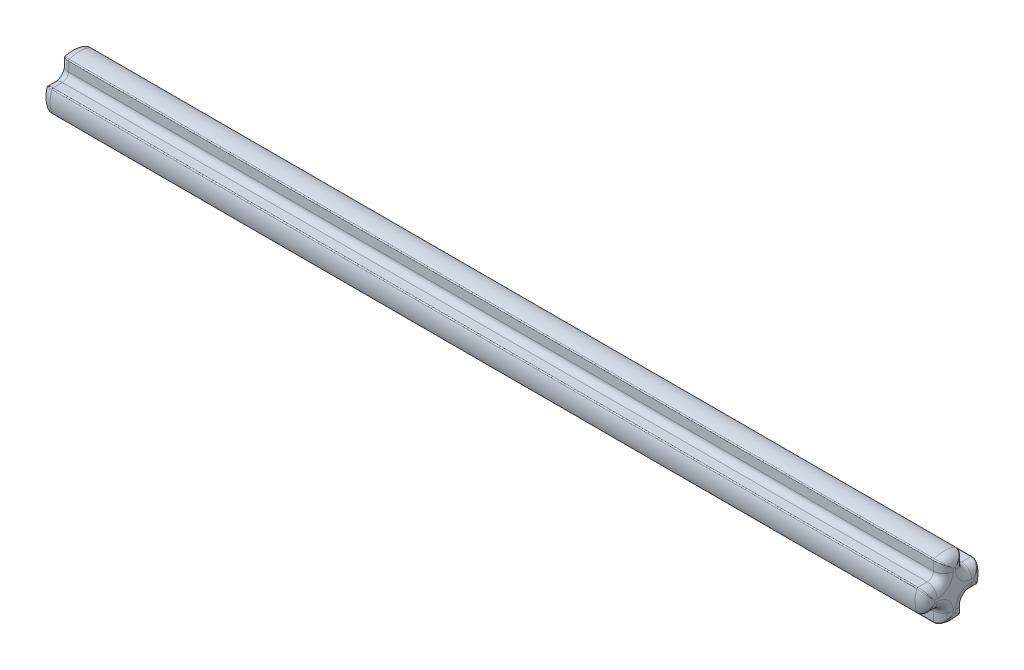
SolidWorks part; units mm, degrees
material "PET"
ref_plane "Alzado" through (0, 0, 0) normal (0, 0, 1) x (1, 0, 0)
ref_plane "Planta" through (0, 0, 0) normal (0, 1, 0) x (1, 0, 0)
ref_plane "Vista lateral" through (0, 0, 0) normal (1, 0, 0) x (0, 0, -1)
sketch "Croquis1" plane through (0, 0, 0) normal (1, 0, 0) x (0, 0, -1)
  line B0 (-1.4, 0.9) -> (-2.2249, 0.9)
  line B1 (0.9, -2.2249) -> (0.9, -1.4)
  line B2 (-0.9, -2.2249) -> (-0.9, -1.4)
  line B3 (2.2249, 0.9) -> (1.4, 0.9)
  line B4 (2.2249, -0.9) -> (1.4, -0.9)
  line B5 (-0.9, 1.4) -> (-0.9, 2.2249)
  line B6 (0.9, 1.4) -> (0.9, 2.2249)
  line B7 (-1.4, -0.9) -> (-2.2249, -0.9)
  arc B8 (-2.2249, 0.9) -> (-2.2249, -0.9) centre (0, 0) ccw
  arc B9 (-1.4, -0.9) -> (-0.9, -1.4) centre (-1.4, -1.4) cw
  arc B10 (0.9, -1.4) -> (1.4, -0.9) centre (1.4, -1.4) cw
  arc B11 (1.4, 0.9) -> (0.9, 1.4) centre (1.4, 1.4) cw
  arc B12 (-0.9, 1.4) -> (-1.4, 0.9) centre (-1.4, 1.4) cw
  arc B13 (0.9, 2.2249) -> (-0.9, 2.2249) centre (0, 0) ccw
  arc B14 (2.2249, -0.9) -> (2.2249, 0.9) centre (0, 0) ccw
  arc B15 (-0.9, -2.2249) -> (0.9, -2.2249) centre (0, 0) ccw
sketch_block_instance "Axle Section Block-1"
sketch_block "Axle Section Block" parameters "D1"=4.8, "D3"=0.5, "D2"=1.8
extrude "Saliente-Extruir1" add sketch "Croquis1" along normal blind 72
fillet "Redondeo1" radius 0.1 8 edges at (36, -2.2249, -0.9) (36, -0.9, -2.2249) (36, 0.9, -2.2249) (36, 2.2249, -0.9) (36, -2.2249, 0.9) (36, 2.2249, 0.9) (36, 0.9, 2.2249) (36, -0.9, 2.2249)
fillet "Redondeo2" radius 0.8 48 edges at (0, -1.0464, -1.0464) (0, -0.9, -1.7782) (0, -0.8821, -2.2135) (0, 0, -2.4) (0, 0.8821, -2.2135) (0, 0.9, -1.7782) (0, 1.0464, -1.0464) (0, 1.7782, -0.9) (0, 2.2135, -0.8821) (0, 2.4, 0) (0, 2.2135, 0.8821) (0, 1.7782, 0.9) (0, 1.0464, 1.0464) (0, 0.9, 1.7782) (0, 0.8821, 2.2135) (0, 0, 2.4) (0, -0.8821, 2.2135) (0, -0.9, 1.7782) (0, -1.0464, 1.0464) (0, -1.7782, 0.9) (0, -2.2135, 0.8821) (0, -2.4, 0) (0, -2.2135, -0.8821) (0, -1.7782, -0.9) (72, -2.2135, 0.8821) (72, -1.7782, 0.9) (72, -1.0464, 1.0464) (72, -0.9, 1.7782) (72, -0.8821, 2.2135) (72, 0, 2.4) (72, 0.8821, 2.2135) (72, 0.9, 1.7782) (72, 1.0464, 1.0464) (72, 1.7782, 0.9) (72, 2.2135, 0.8821) (72, 2.4, 0) (72, 2.2135, -0.8821) (72, 1.7782, -0.9) (72, 1.0464, -1.0464) (72, 0.9, -1.7782) (72, 0.8821, -2.2135) (72, 0, -2.4) (72, -0.8821, -2.2135) (72, -0.9, -1.7782) (72, -1.0464, -1.0464) (72, -1.7782, -0.9) (72, -2.2135, -0.8821) (72, -2.4, 0)
